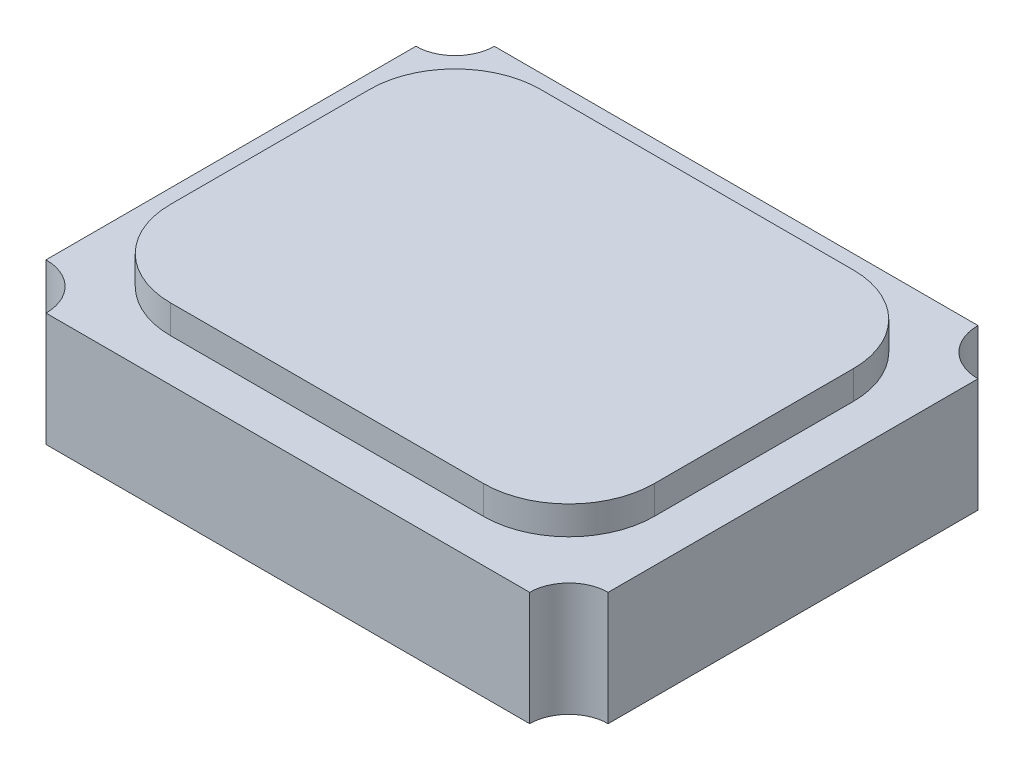
SolidWorks part; units mm, degrees
ref_plane "Front Plane" through (0, 0, 0) normal (0, 0, 1) x (1, 0, 0)
ref_plane "Top Plane" through (0, 0, 0) normal (0, 1, 0) x (1, 0, 0)
ref_plane "Right Plane" through (0, 0, 0) normal (1, 0, 0) x (0, 0, -1)
sketch "Sketch1" plane through (0, 0, 0) normal (0, 1, 0) x (1, 0, 0)
  line L0 (0, 0) -> (2, 0)
  line L1 (2, 0) -> (2, 1.6)
  line L2 (2, 1.6) -> (0, 1.6)
  line L3 (0, 1.6) -> (0, 0)
  dimension "D1" = 2
  dimension "D2" = 1.6
extrude "Boss-Extrude1" add sketch "Sketch1" along normal blind 0.5 contours L0 L1 L2 L3
sketch "Sketch2" plane through (0, 0.5, 0) normal (0, 1, 0) x (1, 0, 0)
  line L0 (0.1379, 1.6) -> (0, 1.4621)
  line L1 (2, 1.6) -> (0, 1.6) construction
  line L2 (0, 1.6) -> (0, 0) construction
  line L3 (0, 1.4621) -> (0, 0.1621)
  line L4 (0, 0.1621) -> (0.1621, 0)
  line L5 (0, 0) -> (2, 0) construction
  line L6 (0.1621, 0) -> (1.8621, 0)
  line L7 (1.8621, 0) -> (2, 0.1379)
  line L8 (2, 0) -> (2, 1.6) construction
  line L9 (2, 0.1379) -> (2, 1.4379)
  line L10 (2, 1.4379) -> (1.8379, 1.6)
  line L11 (1.8379, 1.6) -> (0.1379, 1.6)
  circle A0 centre (0, 1.6) radius 0.1379
  circle A1 centre (2, 1.6) radius 0.1621
  circle A2 centre (2, 0) radius 0.1379
  circle A3 centre (0, 0) radius 0.1621
  line M1 (0, 1.6) -> (0, 0)
  line M2 (0, 0) -> (2, 0)
  line M3 (2, 0) -> (2, 1.6)
  line M4 (2, 1.6) -> (0, 1.6)
  dimension "D1" = 1.7
  dimension "D2" = 1.3
  dimension "D3" = 1.7
  dimension "D4" = 1.3
  dimension "D5" = 135
  dimension "D6" = 135
  dimension "D7" = 135
sketch "Sketch3" plane through (0, 0.5, 0) normal (0, 1, 0) x (1, 0, 0)
  line L0 (0.45, 1.45) -> (1.55, 1.45)
  line L1 (1.85, 1.15) -> (1.85, 0.45)
  line L2 (1.55, 0.15) -> (0.45, 0.15)
  line L3 (0.15, 0.45) -> (0.15, 1.15)
  line L4 (2, 0.1379) -> (2, 1.4379) construction
  line L5 (1.8379, 1.6) -> (0.1379, 1.6) construction
  line L6 (0, 1.6) -> (2, 1.6)
  line L7 (2, 1.6) -> (2, 0)
  line L8 (2, 0) -> (0, 0)
  line L9 (0, 0) -> (0, 1.6)
  arc A0 (1.55, 1.45) -> (1.85, 1.15) centre (1.55, 1.15) cw
  arc A1 (1.85, 0.45) -> (1.55, 0.15) centre (1.55, 0.45) cw
  arc A2 (0.45, 0.15) -> (0.15, 0.45) centre (0.45, 0.45) cw
  arc A3 (0.15, 1.15) -> (0.45, 1.45) centre (0.45, 1.15) cw
  point P10 (1.85, 1.45)
  point P13 (1.85, 0.15)
  point P18 (0.15, 1.45)
  dimension "D5" = 0.3
  dimension "D1" = 1.7
  dimension "D2" = 1.3
  dimension "D3" = 0.15
  dimension "D4" = 0.15
extrude "Cut-Extrude1" cut sketch "Sketch3" against normal blind 0.1
extrude "Cut-Extrude2" cut sketch "Sketch2" against normal blind 0.5 contours L0 M4 M1 | L0 A0 | L10 A1 | L10 M3 M4 | L7 M2 M3 | L7 A2 | L4 M1 M2 | L4 A3 region at (0.0805, 0.5, -1.5195) region at (0.046, 0.5, -1.554) region at (1.946, 0.5, -1.546) region at (1.9053, 0.5, -1.5053) region at (0.0947, 0.5, -0.0947) region at (0.054, 0.5, -0.054) region at (1.954, 0.5, -0.046) region at (1.9195, 0.5, -0.0805)
